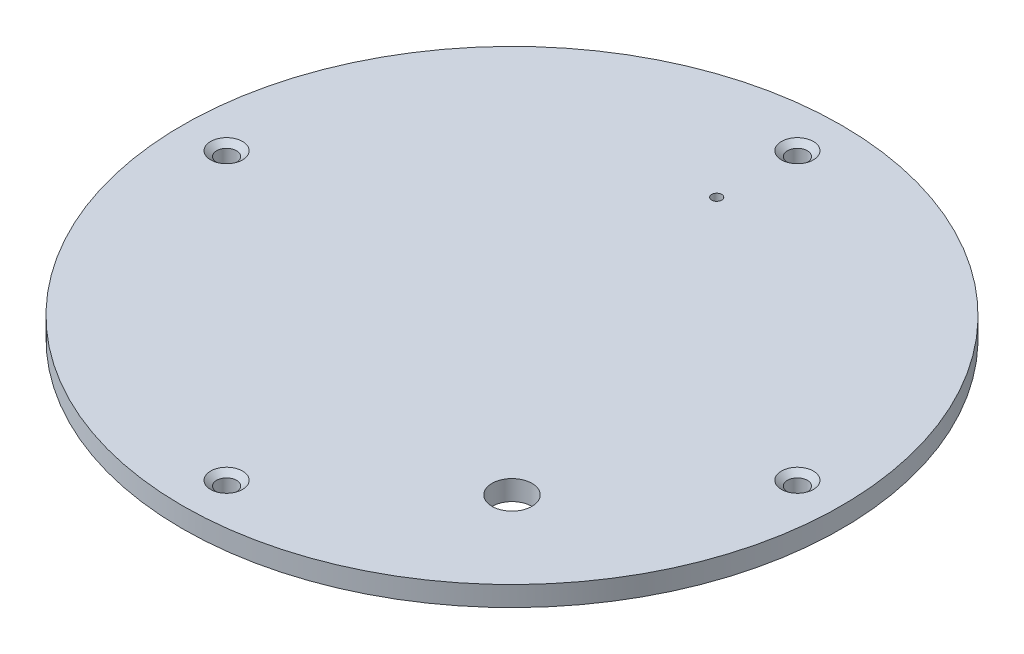
SolidWorks part; units mm, degrees
material "1060 Alloy"
ref_plane "Front Plane" through (0, 0, 0) normal (0, 0, 1) x (1, 0, 0)
ref_plane "Top Plane" through (0, 0, 0) normal (0, 1, 0) x (1, 0, 0)
ref_plane "Right Plane" through (0, 0, 0) normal (1, 0, 0) x (0, 0, -1)
sketch "Sketch1" plane through (0, 0, 0) normal (0, 1, 0) x (1, 0, 0)
  circle A0 centre (0, 0) radius 16.5
  dimension "D1" = 33
extrude "Boss-Extrude1" add sketch "Sketch1" along normal blind 1
sketch "Sketch6" plane through (0, 1, 0) normal (0, 1, 0) x (1, 0, 0)
  line L0 (0, 0) -> (14.1535, -14.1535) construction
  line L1 (0, 0) -> (17.9741, 0) construction
  circle A0 centre (0, 10.25) radius 0.25
  circle A1 centre (7.7782, -7.7782) radius 1
  dimension "D1" = 10.25
  dimension "D3" = 0.5
  dimension "D4" = 2
  dimension "D2" = 0
  dimension "D5" = 11
  dimension "D6" = 45
extrude "Cut-Extrude1" cut sketch "Sketch6" against normal through all both and the other way through all
hole_wizard "CSK for M2 Flat Head Machine Screw1" positions "Sketch7" profile "Sketch8" countersink size "M2" standard "ANSI Metric" end condition through all
sketch "Sketch7" plane through (0, 1, 0) normal (0, 1, 0) x (1, 0, 0)
  point P0 (0, 14.29)
  point P2 (-14.29, 0)
  point P4 (0, -14.29)
  point P6 (14.29, 0)
  dimension "D1" = 14.29
  dimension "D2" = 14.29
  dimension "D3" = 14.29
  dimension "D4" = 14.29
sketch "Sketch8" plane through (0, 1, -14.29) normal (1, 0, 0) x (0, 0, 1)
  line L0 (0, 0) -> (0, 1)
  line L1 (0, 1) -> (0.5, 1)
  line L2 (0.5, 1) -> (0.5, 0.2517)
  line L3 (0.5, 0.2517) -> (0.8, 0)
  line L5 (0.8, 0) -> (0, 0)
  line L6 (-0.5, 0.2517) -> (-0.8, 0) construction
  line L11 (0, -6.35) -> (0, 107.95) construction
  dimension "Thru Hole Dia." = 1
  dimension "Thru Hole Depth" = 1
  dimension "Near C'Sink Dia." = 1.6
  dimension "Near C'Sink Angle" = 100
